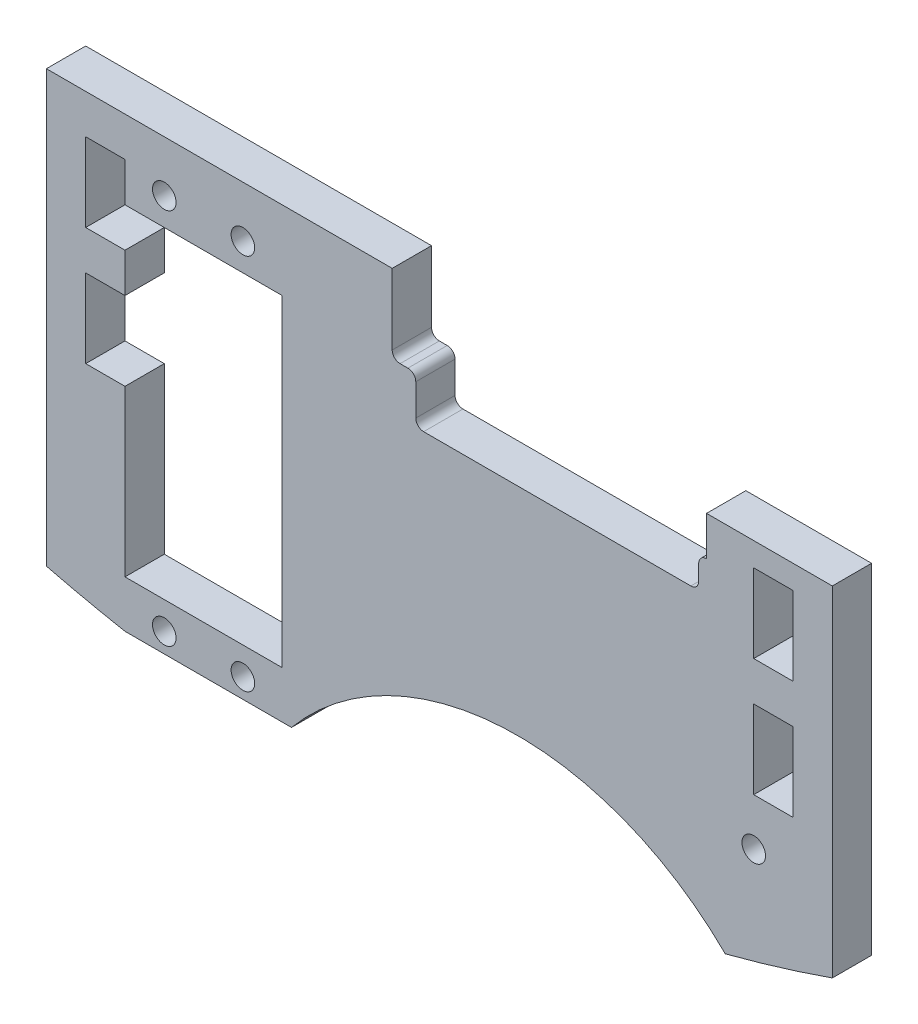
SolidWorks part; units mm, degrees
ref_plane "Plan de face" through (0, 0, 0) normal (0, 0, 1) x (1, 0, 0)
ref_plane "Plan de dessus" through (0, 0, 0) normal (0, 1, 0) x (1, 0, 0)
ref_plane "Plan de droite" through (0, 0, 0) normal (1, 0, 0) x (0, 0, -1)
sketch "Esquisse1" plane through (0, 0, 0) normal (0, 0, 1) x (1, 0, 0)
  line L0 (20, 67) -> (20, -4) construction
  line L1 (0, 0) -> (31.1859, 0)
  line L2 (0, 0) -> (0, 57)
  line L3 (0, 57) -> (44, 57)
  line L4 (100, 0) -> (100, 50)
  line L5 (10, 26.5) -> (30, 26.5) construction
  line L6 (10, 47) -> (19, 47)
  line L7 (10, 42) -> (10, 37)
  line L8 (10, 6) -> (19, 6)
  line L9 (30, 47) -> (30, 6)
  line L10 (20, 16) -> (90, 16) construction
  line L11 (88.8141, 0) -> (100, 0)
  line L15 (19, 6) -> (30, 6)
  line L19 (19, 47) -> (30, 47)
  line L20 (10, 27) -> (10, 6)
  line L21 (90, 47) -> (95, 47)
  line L22 (90, 47) -> (90, 37)
  line L23 (90, 37) -> (95, 37)
  line L24 (95, 47) -> (95, 37)
  line L25 (90, 32) -> (95, 32)
  line L26 (90, 32) -> (90, 22)
  line L27 (90, 22) -> (95, 22)
  line L28 (95, 32) -> (95, 22)
  line L29 (5, 52) -> (10, 52)
  line L30 (5, 52) -> (5, 42)
  line L31 (5, 42) -> (10, 42)
  line L32 (10, 52) -> (10, 47)
  line L33 (5, 37) -> (10, 37)
  line L34 (5, 37) -> (5, 27)
  line L35 (5, 27) -> (10, 27)
  line L36 (84, 50) -> (100, 50)
  line L37 (47, 47) -> (44, 47)
  line L38 (84, 50) -> (84, 45)
  line L39 (84, 45) -> (83, 45)
  line L40 (44, 57) -> (44, 47)
  line L42 (83, 45) -> (83, 41)
  line L43 (83, 41) -> (47, 41)
  line L44 (47, 47) -> (47, 41)
  circle A0 centre (15, 2.5) radius 1.5
  circle A1 centre (25, 2.5) radius 1.5
  circle A2 centre (25, 50.5) radius 1.5
  circle A3 centre (15, 50.5) radius 1.5
  circle A4 centre (20, 16) radius 1.5 construction
  circle A5 centre (20, 16) radius 1.5 construction
  circle A6 centre (90, 16) radius 1.5
  circle A7 centre (60, -24) radius 37.5 construction
  arc A8 (31.1859, 0) -> (88.8141, 0) centre (60, -24) cw
  dimension "D6" = 3.5
  dimension "D8" = 3
  dimension "D9" = 3
  dimension "D10" = 70
  dimension "D13" = 75
  dimension "D1" = 6
  dimension "D2" = 41
  dimension "D3" = 20
  dimension "D4" = 10
  dimension "D5" = 100
  dimension "D7" = 5
  dimension "D11" = 10
  dimension "D12" = 10
  dimension "D14" = 40
  dimension "D15" = 40
  dimension "D18" = 5
  dimension "D19" = 5
  dimension "D20" = 10
  dimension "D21" = 3
  dimension "D22" = 5
  dimension "D23" = 5
  dimension "D24" = 10
  dimension "D25" = 6
  dimension "D26" = 10
  dimension "D27" = 40
  dimension "D28" = 1
  dimension "D29" = 36
  dimension "D30" = 5
  dimension "D31" = 5
  dimension "D32" = 4
  dimension "D33" = 5
  dimension "D34" = 50
extrude "Boss.-Extru.1" add sketch "Esquisse1" along normal blind 5
fillet "Congé1" radius 1 5 edges at (83, 45, 2.5) (83, 41, 2.5) (47, 41, 2.5) (47, 47, 2.5) (44, 47, 2.5)
sketch "Esquisse2" plane through (0, 0, 5) normal (0, 0, 1) x (1, 0, 0)
  line L0 (0, 0) -> (31.1859, 0) construction
  line L1 (10, 27) -> (10, 6) construction
  line L2 (-40.4936, 0.9705) -> (-34.879, 14.9208)
  line L3 (159.5405, 42.1102) -> (167.1741, 28.8302)
  arc A0 (-34.879, 14.9208) -> (159.5405, 42.1102) centre (42.2645, 172) ccw
  arc A1 (-40.4936, 0.9705) -> (167.1741, 28.8302) centre (42.2645, 172) ccw
  point P3 (10, 0)
  dimension "D1" = 175
  dimension "D2" = 15
  dimension "D3" = 172
extrude "Enlèv. mat.-Extru.1" cut sketch "Esquisse2" against normal blind 10
